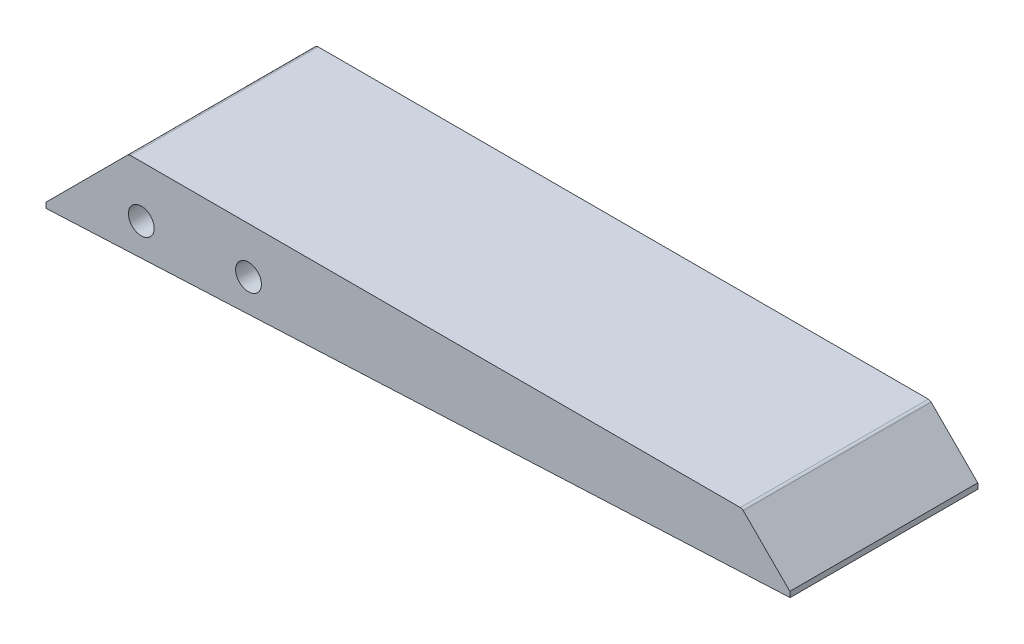
SolidWorks part; units mm, degrees
ref_plane "前视基准面" through (0, 0, 0) normal (0, 0, 1) x (1, 0, 0)
ref_plane "上视基准面" through (0, 0, 0) normal (0, 1, 0) x (1, 0, 0)
ref_plane "右视基准面" through (0, 0, 0) normal (1, 0, 0) x (0, 0, -1)
other "Configuration Table"
sketch "草图1" plane through (0, 0, 0) normal (0, 0, 1) x (1, 0, 0)
  line L0 (168.3324, 7.5944) -> (170.4537, 9.7157) construction
  line L1 (170.4537, 9.7157) -> (161.7639, 18.4056) construction
  line L2 (159.6425, 16.2843) -> (168.3324, 7.5944) construction
  line L3 (159.1217, 19.5) -> (45.4745, 19.5) construction
  line L4 (45.4745, 16.5) -> (159.1217, 16.5) construction
  line L5 (29.7639, 1.0944) -> (44.9537, 16.2843) construction
  line L6 (42.8324, 18.4056) -> (27.6425, 3.2157) construction
  line L7 (27.6425, 3.2157) -> (29.7639, 1.0944) construction
  line L8 (168.3324, 7.5944) -> (170.4537, 9.7157)
  line L9 (170.4537, 9.7157) -> (161.7639, 18.4056)
  line L10 (159.6425, 16.2843) -> (168.3324, 7.5944)
  line L11 (159.1217, 19.5) -> (45.4745, 19.5)
  line L12 (45.4745, 16.5) -> (159.1217, 16.5)
  line L13 (29.7639, 1.0944) -> (44.9537, 16.2843)
  line L14 (42.8324, 18.4056) -> (27.6425, 3.2157)
  line L15 (27.6425, 3.2157) -> (29.7639, 1.0944)
  line L16 (29.7639, 1.0944) -> (168.3324, 7.5944)
  arc A0 (159.6425, 16.2843) -> (159.1217, 16.5) centre (159.1217, 15.7634) ccw construction
  arc A1 (161.7639, 18.4056) -> (159.1217, 19.5) centre (159.1217, 15.7634) ccw construction
  arc A2 (45.4745, 16.5) -> (44.9537, 16.2843) centre (45.4745, 15.7634) ccw construction
  arc A3 (45.4745, 19.5) -> (42.8324, 18.4056) centre (45.4745, 15.7634) ccw construction
  arc A4 (159.6425, 16.2843) -> (159.1217, 16.5) centre (159.1217, 15.7634) ccw
  arc A5 (161.7639, 18.4056) -> (159.1217, 19.5) centre (159.1217, 15.7634) ccw
  arc A6 (45.4745, 16.5) -> (44.9537, 16.2843) centre (45.4745, 15.7634) ccw
  arc A7 (45.4745, 19.5) -> (42.8324, 18.4056) centre (45.4745, 15.7634) ccw
extrude "凸台-拉伸1" add sketch "草图1" against normal blind 35 contours L12 A6 L13 L16 L10 A4 region at (95.4976, 10.1082, 0)
sketch "草图2" plane through (0.0141, -0.3011, 0) normal (0.0469, -0.9989, 0) x (0.9989, 0.0469, 0)
  line L0 (167.0033, -1.5) -> (31.2825, -1.5)
  line L1 (31.2825, -1.5) -> (31.2825, -33.5)
  line L2 (31.2825, -33.5) -> (167.0033, -33.5)
  line L3 (167.0033, -33.5) -> (167.0033, -1.5)
  line L4 (168.5033, 0) -> (29.7825, 0)
  line L5 (29.7825, 0) -> (29.7825, -35)
  line L6 (29.7825, -35) -> (168.5033, -35)
  line L7 (168.5033, -35) -> (168.5033, 0)
  line L8 (168.5033, 0) -> (29.7825, 0)
  line L9 (29.7825, 0) -> (29.7825, -35)
  line L10 (29.7825, -35) -> (168.5033, -35)
  line L11 (168.5033, -35) -> (168.5033, 0)
  dimension "D1" = 0
  dimension "D2" = 1.5
extrude "凸台-拉伸2" add sketch "草图2" along normal blind 1
fillet "圆角1" radius 2 4 edges at (31.2856, 0.6653, -33.5) (166.8575, 7.0247, -33.5) (166.8575, 7.0247, -1.5) (31.2856, 0.6653, -1.5)
sketch "草图3" plane through (0, 0, 0) normal (0, 0, 1) x (1, 0, 0)
  line L0 (168.3792, 6.5955) -> (29.8107, 0.0955) construction
  line L1 (29.8107, 0.0955) -> (29.7639, 1.0944) construction
  circle A0 centre (47.5098, 6.9324) radius 2.4
  circle A1 centre (67.4872, 7.8832) radius 2.4
  dimension "D1" = 4.8
  dimension "D3" = 20
  dimension "D4" = 6
  dimension "D5" = 18
  dimension "D2" = 2
extrude "切除-拉伸1" cut sketch "草图3" against normal blind 6.2
sketch "草图4" plane through (0, 0, -35) normal (0, 0, -1) x (-1, 0, 0)
  circle A0 centre (-47.5098, 6.9324) radius 2.4 construction
  circle A1 centre (-67.4872, 7.8832) radius 2.4 construction
  circle A2 centre (-47.5098, 6.9324) radius 2.4
  circle A3 centre (-67.4872, 7.8832) radius 2.4
extrude "切除-拉伸2" cut sketch "草图4" against normal blind 6.55
sketch "草图6" plane through (0.0141, -0.3011, 0) normal (0.0469, -0.9989, 0) x (0.9989, 0.0469, 0)
  line L1199 (144.5332, -18.3417) -> (144.2984, -18.2008)
  line L1200 (144.2984, -18.2008) -> (143.9227, -18.2947)
  line L1201 (143.9227, -18.2947) -> (142.7956, -19.4688)
  line L1202 (142.7956, -19.4688) -> (142.279, -19.8915)
  line L1203 (142.279, -19.8915) -> (142.1381, -19.8915)
  line L1204 (142.1381, -19.8915) -> (142.0911, -19.7506)
  line L1205 (142.0911, -19.7506) -> (142.6547, -18.2478)
  line L1206 (142.6547, -18.2478) -> (142.7016, -17.8251)
  line L1207 (142.7016, -17.8251) -> (142.4668, -17.4963)
  line L1208 (142.4668, -17.4963) -> (141.9972, -17.4494)
  line L1209 (141.9972, -17.4494) -> (141.6684, -17.7312)
  line L1210 (141.6684, -17.7312) -> (141.2457, -18.3887)
  line L1211 (141.2457, -18.3887) -> (140.2595, -19.3749)
  line L1212 (140.2595, -19.3749) -> (139.2263, -20.1263)
  line L1213 (139.2263, -20.1263) -> (138.8036, -20.3142)
  line L1214 (138.8036, -20.3142) -> (138.6157, -20.3142)
  line L1215 (138.6157, -20.3142) -> (138.5218, -20.2203)
  line L1216 (138.5218, -20.2203) -> (138.5218, -19.9854)
  line L1217 (138.5218, -19.9854) -> (138.6627, -19.6097)
  line L1218 (138.6627, -19.6097) -> (139.4611, -18.4356)
  line L1219 (139.4611, -18.4356) -> (139.4611, -18.1069)
  line L1220 (139.4611, -18.1069) -> (139.2732, -17.872)
  line L1221 (139.2732, -17.872) -> (139.0384, -17.7781)
  line L1222 (139.0384, -17.7781) -> (138.6627, -17.872)
  line L1223 (138.6627, -17.872) -> (138.0052, -18.6235)
  line L1224 (138.0052, -18.6235) -> (137.5825, -19.3279)
  line L1225 (137.5825, -19.3279) -> (137.3477, -20.1263)
  line L1226 (137.3477, -20.1263) -> (137.3477, -20.4081)
  line L1227 (137.3477, -20.4081) -> (137.4886, -20.7838)
  line L1228 (137.4886, -20.7838) -> (137.9113, -21.1595)
  line L1229 (137.9113, -21.1595) -> (138.1931, -21.2535)
  line L1230 (138.1931, -21.2535) -> (138.7566, -21.2535)
  line L1231 (138.7566, -21.2535) -> (139.6959, -20.8778)
  line L1232 (139.6959, -20.8778) -> (140.6352, -20.1733)
  line L1233 (140.6352, -20.1733) -> (140.7761, -20.2203)
  line L1234 (140.7761, -20.2203) -> (140.6352, -20.8308)
  line L1235 (140.6352, -20.8308) -> (140.5413, -20.9247)
  line L1236 (140.5413, -20.9247) -> (138.5218, -21.817)
  line L1237 (138.5218, -21.817) -> (137.9582, -22.1928)
  line L1238 (137.9582, -22.1928) -> (137.6295, -22.5215)
  line L1239 (137.6295, -22.5215) -> (137.4416, -22.8503)
  line L1240 (137.4416, -22.8503) -> (137.4416, -23.2729)
  line L1241 (137.4416, -23.2729) -> (137.6765, -23.6487)
  line L1242 (137.6765, -23.6487) -> (138.0052, -23.8835)
  line L1243 (138.0052, -23.8835) -> (138.3809, -24.0244)
  line L1244 (138.3809, -24.0244) -> (139.1793, -24.0713)
  line L1245 (139.1793, -24.0713) -> (139.8368, -23.8835)
  line L1246 (139.8368, -23.8835) -> (140.4473, -23.5078)
  line L1247 (140.4473, -23.5078) -> (141.0109, -22.8503)
  line L1248 (141.0109, -22.8503) -> (141.4806, -21.817)
  line L1249 (141.4806, -21.817) -> (141.6215, -21.3004)
  line L1250 (141.6215, -21.3004) -> (142.8425, -20.596)
  line L1251 (142.8425, -20.596) -> (143.7348, -19.8445)
  line L1252 (143.7348, -19.8445) -> (144.4863, -18.9522)
  line L1253 (144.4863, -18.9522) -> (144.5802, -18.7644)
  line L1254 (144.5802, -18.7644) -> (144.5332, -18.3417)
  line L1255 (140.2125, -21.9579) -> (140.2125, -22.0988)
  line L1256 (140.2125, -22.0988) -> (140.0247, -22.4745)
  line L1257 (140.0247, -22.4745) -> (139.555, -22.9912)
  line L1258 (139.555, -22.9912) -> (139.0854, -23.226)
  line L1259 (139.0854, -23.226) -> (138.6627, -23.226)
  line L1260 (138.6627, -23.226) -> (138.5218, -23.0851)
  line L1261 (138.5218, -23.0851) -> (138.5688, -22.8503)
  line L1262 (138.5688, -22.8503) -> (138.8036, -22.5685)
  line L1263 (138.8036, -22.5685) -> (140.0716, -21.911)
  line L1264 (140.0716, -21.911) -> (140.2125, -21.9579)
  line L1265 (156.9788, -14.8663) -> (156.744, -14.7254)
  line L1266 (156.744, -14.7254) -> (156.4152, -14.7254)
  line L1267 (156.4152, -14.7254) -> (156.1334, -14.9133)
  line L1268 (156.1334, -14.9133) -> (156.0395, -15.1481)
  line L1269 (156.0395, -15.1481) -> (155.9925, -16.0874)
  line L1270 (155.9925, -16.0874) -> (155.5698, -17.1676)
  line L1271 (155.5698, -17.1676) -> (154.7715, -18.3417)
  line L1272 (154.7715, -18.3417) -> (153.9731, -19.0462)
  line L1273 (153.9731, -19.0462) -> (153.6913, -18.9992)
  line L1274 (153.6913, -18.9992) -> (153.6913, -18.3417)
  line L1275 (153.6913, -18.3417) -> (153.8791, -17.7312)
  line L1276 (153.8791, -17.7312) -> (153.8791, -17.3085)
  line L1277 (153.8791, -17.3085) -> (153.6913, -17.0736)
  line L1278 (153.6913, -17.0736) -> (153.5034, -16.9797)
  line L1279 (153.5034, -16.9797) -> (153.2686, -16.9797)
  line L1280 (153.2686, -16.9797) -> (153.0338, -17.0736)
  line L1281 (153.0338, -17.0736) -> (152.8459, -17.2615)
  line L1282 (152.8459, -17.2615) -> (152.3763, -18.1069)
  line L1283 (152.3763, -18.1069) -> (151.39, -19.1401)
  line L1284 (151.39, -19.1401) -> (151.1082, -19.3279)
  line L1285 (151.1082, -19.3279) -> (150.9204, -19.281)
  line L1286 (150.9204, -19.281) -> (150.9673, -18.9053)
  line L1287 (150.9673, -18.9053) -> (151.2022, -18.2478)
  line L1288 (151.2022, -18.2478) -> (152.0006, -16.7919)
  line L1289 (152.0006, -16.7919) -> (151.9536, -16.3692)
  line L1290 (151.9536, -16.3692) -> (151.5779, -16.1344)
  line L1291 (151.5779, -16.1344) -> (151.2022, -16.2283)
  line L1292 (151.2022, -16.2283) -> (150.9204, -16.5101)
  line L1293 (150.9204, -16.5101) -> (150.122, -17.872)
  line L1294 (150.122, -17.872) -> (149.8872, -18.6235)
  line L1295 (149.8872, -18.6235) -> (149.0418, -19.4219)
  line L1296 (149.0418, -19.4219) -> (148.4782, -19.8445)
  line L1297 (148.4782, -19.8445) -> (148.2434, -19.9385)
  line L1298 (148.2434, -19.9385) -> (147.9616, -19.9385)
  line L1299 (147.9616, -19.9385) -> (147.7268, -19.7976)
  line L1300 (147.7268, -19.7976) -> (147.3511, -19.4219)
  line L1301 (147.3511, -19.4219) -> (147.3511, -19.281)
  line L1302 (147.3511, -19.281) -> (149.1827, -17.5433)
  line L1303 (149.1827, -17.5433) -> (149.2766, -17.3554)
  line L1304 (149.2766, -17.3554) -> (149.2766, -17.1206)
  line L1305 (149.2766, -17.1206) -> (149.0418, -16.8388)
  line L1306 (149.0418, -16.8388) -> (148.6661, -16.7919)
  line L1307 (148.6661, -16.7919) -> (148.3373, -16.9328)
  line L1308 (148.3373, -16.9328) -> (146.6466, -18.4826)
  line L1309 (146.6466, -18.4826) -> (146.5057, -18.4826)
  line L1310 (146.5057, -18.4826) -> (145.6604, -17.5433)
  line L1311 (145.6604, -17.5433) -> (145.1907, -17.4963)
  line L1312 (145.1907, -17.4963) -> (145.0029, -17.5903)
  line L1313 (145.0029, -17.5903) -> (144.815, -17.8251)
  line L1314 (144.815, -17.8251) -> (144.815, -18.1069)
  line L1315 (144.815, -18.1069) -> (145.7543, -19.281)
  line L1316 (145.7543, -19.281) -> (145.7543, -19.3749)
  line L1317 (145.7543, -19.3749) -> (144.1106, -21.2065)
  line L1318 (144.1106, -21.2065) -> (143.9227, -21.5822)
  line L1319 (143.9227, -21.5822) -> (143.9697, -21.864)
  line L1320 (143.9697, -21.864) -> (144.2515, -22.0988)
  line L1321 (144.2515, -22.0988) -> (144.5802, -22.0988)
  line L1322 (144.5802, -22.0988) -> (144.815, -22.0049)
  line L1323 (144.815, -22.0049) -> (146.4588, -20.2203)
  line L1324 (146.4588, -20.2203) -> (146.5997, -20.2203)
  line L1325 (146.5997, -20.2203) -> (147.0693, -20.6429)
  line L1326 (147.0693, -20.6429) -> (147.492, -20.8778)
  line L1327 (147.492, -20.8778) -> (148.2904, -20.9247)
  line L1328 (148.2904, -20.9247) -> (149.0888, -20.549)
  line L1329 (149.0888, -20.549) -> (149.7463, -19.9385)
  line L1330 (149.7463, -19.9385) -> (149.8872, -19.9385)
  line L1331 (149.8872, -19.9385) -> (150.169, -20.2672)
  line L1332 (150.169, -20.2672) -> (150.4038, -20.4081)
  line L1333 (150.4038, -20.4081) -> (150.9204, -20.4551)
  line L1334 (150.9204, -20.4551) -> (151.2491, -20.3611)
  line L1335 (151.2491, -20.3611) -> (151.8127, -20.0324)
  line L1336 (151.8127, -20.0324) -> (152.5172, -19.3749)
  line L1337 (152.5172, -19.3749) -> (152.6581, -19.4219)
  line L1338 (152.6581, -19.4219) -> (152.752, -19.6567)
  line L1339 (152.752, -19.6567) -> (153.0338, -19.9385)
  line L1340 (153.0338, -19.9385) -> (153.4565, -20.1263)
  line L1341 (153.4565, -20.1263) -> (154.067, -20.0794)
  line L1342 (154.067, -20.0794) -> (154.5366, -19.8915)
  line L1343 (154.5366, -19.8915) -> (155.2881, -19.3279)
  line L1344 (155.2881, -19.3279) -> (155.7577, -18.8583)
  line L1345 (155.7577, -18.8583) -> (156.2743, -18.1538)
  line L1346 (156.2743, -18.1538) -> (156.744, -17.3085)
  line L1347 (156.744, -17.3085) -> (157.1197, -16.0404)
  line L1348 (157.1197, -16.0404) -> (157.1197, -15.1951)
  line L1349 (157.1197, -15.1951) -> (156.9788, -14.8663)
  line L1599 (103.178, -10.8157) -> (102.5205, -10.4869)
  line L1600 (102.5205, -10.4869) -> (101.7221, -10.2521)
  line L1601 (101.7221, -10.2521) -> (100.2192, -10.2521)
  line L1602 (100.2192, -10.2521) -> (99.5148, -10.5339)
  line L1603 (99.5148, -10.5339) -> (99.0921, -10.8626)
  line L1604 (99.0921, -10.8626) -> (97.4014, -11.6141)
  line L1605 (97.4014, -11.6141) -> (95.8985, -12.1307)
  line L1606 (95.8985, -12.1307) -> (94.8653, -12.2716)
  line L1607 (94.8653, -12.2716) -> (94.6305, -12.4594)
  line L1608 (94.6305, -12.4594) -> (94.5365, -12.6473)
  line L1609 (94.5365, -12.6473) -> (94.5835, -12.9291)
  line L1610 (94.5835, -12.9291) -> (95.0531, -13.3987)
  line L1611 (95.0531, -13.3987) -> (95.4289, -13.5866)
  line L1612 (95.4289, -13.5866) -> (96.0864, -13.7744)
  line L1613 (96.0864, -13.7744) -> (97.6362, -13.7744)
  line L1614 (97.6362, -13.7744) -> (97.824, -14.1032)
  line L1615 (97.824, -14.1032) -> (97.871, -14.9955)
  line L1616 (97.871, -14.9955) -> (97.7771, -15.3242)
  line L1617 (97.7771, -15.3242) -> (96.556, -15.7939)
  line L1618 (96.556, -15.7939) -> (95.8046, -16.2635)
  line L1619 (95.8046, -16.2635) -> (94.9592, -15.9817)
  line L1620 (94.9592, -15.9817) -> (94.4896, -15.9817)
  line L1621 (94.4896, -15.9817) -> (94.1608, -16.1226)
  line L1622 (94.1608, -16.1226) -> (94.0199, -16.2635)
  line L1623 (94.0199, -16.2635) -> (93.926, -16.5453)
  line L1624 (93.926, -16.5453) -> (94.2078, -17.4846)
  line L1625 (94.2078, -17.4846) -> (94.2548, -18.8935)
  line L1626 (94.2548, -18.8935) -> (94.3956, -19.7389)
  line L1627 (94.3956, -19.7389) -> (94.6305, -20.3964)
  line L1628 (94.6305, -20.3964) -> (94.9123, -20.866)
  line L1629 (94.9123, -20.866) -> (95.4758, -21.4296)
  line L1630 (95.4758, -21.4296) -> (95.9924, -21.6644)
  line L1631 (95.9924, -21.6644) -> (96.603, -21.7114)
  line L1632 (96.603, -21.7114) -> (97.3544, -21.4766)
  line L1633 (97.3544, -21.4766) -> (97.5423, -21.4766)
  line L1634 (97.5423, -21.4766) -> (97.5892, -21.6644)
  line L1635 (97.5892, -21.6644) -> (97.4483, -22.3219)
  line L1636 (97.4483, -22.3219) -> (97.2605, -22.7916)
  line L1637 (97.2605, -22.7916) -> (96.7908, -23.3551)
  line L1638 (96.7908, -23.3551) -> (95.1471, -23.8248)
  line L1639 (95.1471, -23.8248) -> (93.6442, -24.1066)
  line L1640 (93.6442, -24.1066) -> (92.7519, -24.1535)
  line L1641 (92.7519, -24.1535) -> (92.4701, -24.2944)
  line L1642 (92.4701, -24.2944) -> (92.1883, -24.6232)
  line L1643 (92.1883, -24.6232) -> (92.0944, -25.0928)
  line L1644 (92.0944, -25.0928) -> (92.3292, -25.6564)
  line L1645 (92.3292, -25.6564) -> (92.7519, -26.0791)
  line L1646 (92.7519, -26.0791) -> (93.4094, -26.4548)
  line L1647 (93.4094, -26.4548) -> (93.973, -26.6426)
  line L1648 (93.973, -26.6426) -> (95.5228, -26.6426)
  line L1649 (95.5228, -26.6426) -> (96.4621, -26.4078)
  line L1650 (96.4621, -26.4078) -> (100.5949, -24.905)
  line L1651 (100.5949, -24.905) -> (102.9431, -24.2005)
  line L1652 (102.9431, -24.2005) -> (103.3658, -24.2475)
  line L1653 (103.3658, -24.2475) -> (103.9764, -25.2807)
  line L1654 (103.9764, -25.2807) -> (104.446, -25.7034)
  line L1655 (104.446, -25.7034) -> (104.9156, -25.9382)
  line L1656 (104.9156, -25.9382) -> (105.3853, -26.0321)
  line L1657 (105.3853, -26.0321) -> (105.9019, -25.9851)
  line L1658 (105.9019, -25.9851) -> (106.4185, -25.7503)
  line L1659 (106.4185, -25.7503) -> (106.7942, -25.3746)
  line L1660 (106.7942, -25.3746) -> (107.029, -24.7641)
  line L1661 (107.029, -24.7641) -> (107.029, -24.2005)
  line L1662 (107.029, -24.2005) -> (106.8881, -23.6839)
  line L1663 (106.8881, -23.6839) -> (106.5594, -23.1203)
  line L1664 (106.5594, -23.1203) -> (105.8549, -22.3689)
  line L1665 (105.8549, -22.3689) -> (104.9156, -21.7114)
  line L1666 (104.9156, -21.7114) -> (103.8824, -21.2417)
  line L1667 (103.8824, -21.2417) -> (103.178, -21.0539)
  line L1668 (103.178, -21.0539) -> (102.6144, -21.1009)
  line L1669 (102.6144, -21.1009) -> (102.4265, -21.1948)
  line L1670 (102.4265, -21.1948) -> (102.2387, -21.4766)
  line L1671 (102.2387, -21.4766) -> (102.3326, -21.8523)
  line L1672 (102.3326, -21.8523) -> (102.6144, -22.181)
  line L1673 (102.6144, -22.181) -> (102.5205, -22.3689)
  line L1674 (102.5205, -22.3689) -> (101.2524, -22.5567)
  line L1675 (101.2524, -22.5567) -> (100.2662, -22.7916)
  line L1676 (100.2662, -22.7916) -> (99.9374, -22.7446)
  line L1677 (99.9374, -22.7446) -> (99.9374, -22.6037)
  line L1678 (99.9374, -22.6037) -> (100.2662, -21.9462)
  line L1679 (100.2662, -21.9462) -> (100.5949, -20.7721)
  line L1680 (100.5949, -20.7721) -> (100.7358, -20.6782)
  line L1681 (100.7358, -20.6782) -> (101.5342, -20.4903)
  line L1682 (101.5342, -20.4903) -> (102.8492, -20.3494)
  line L1683 (102.8492, -20.3494) -> (103.5067, -20.1146)
  line L1684 (103.5067, -20.1146) -> (103.8355, -19.7859)
  line L1685 (103.8355, -19.7859) -> (103.9764, -19.4571)
  line L1686 (103.9764, -19.4571) -> (104.5399, -18.6587)
  line L1687 (104.5399, -18.6587) -> (105.3383, -17.015)
  line L1688 (105.3383, -17.015) -> (105.3383, -16.3575)
  line L1689 (105.3383, -16.3575) -> (105.2444, -16.0757)
  line L1690 (105.2444, -16.0757) -> (105.0096, -15.7)
  line L1691 (105.0096, -15.7) -> (104.1642, -14.9955)
  line L1692 (104.1642, -14.9955) -> (103.6006, -14.7137)
  line L1693 (103.6006, -14.7137) -> (102.5674, -14.4319)
  line L1694 (102.5674, -14.4319) -> (101.5812, -14.4319)
  line L1695 (101.5812, -14.4319) -> (101.2524, -14.5259)
  line L1696 (101.2524, -14.5259) -> (100.8298, -14.4789)
  line L1697 (100.8298, -14.4789) -> (100.7828, -13.9623)
  line L1698 (100.7828, -13.9623) -> (100.6889, -13.7744)
  line L1699 (100.6889, -13.7744) -> (100.6889, -13.6335)
  line L1700 (100.6889, -13.6335) -> (100.7828, -13.5396)
  line L1701 (100.7828, -13.5396) -> (103.2249, -12.9291)
  line L1702 (103.2249, -12.9291) -> (103.7885, -12.4594)
  line L1703 (103.7885, -12.4594) -> (103.9294, -12.1307)
  line L1704 (103.9294, -12.1307) -> (103.8824, -11.6141)
  line L1705 (103.8824, -11.6141) -> (103.7415, -11.3323)
  line L1706 (103.7415, -11.3323) -> (103.178, -10.8157)
  line L1707 (97.7301, -17.2967) -> (97.7301, -19.3162)
  line L1708 (97.7301, -19.3162) -> (97.4014, -19.551)
  line L1709 (97.4014, -19.551) -> (96.8848, -19.598)
  line L1710 (96.8848, -19.598) -> (96.6969, -19.4571)
  line L1711 (96.6969, -19.4571) -> (96.556, -19.0344)
  line L1712 (96.556, -19.0344) -> (96.509, -17.9073)
  line L1713 (96.509, -17.9073) -> (96.6499, -17.7664)
  line L1714 (96.6499, -17.7664) -> (97.5892, -17.2967)
  line L1715 (97.5892, -17.2967) -> (97.7301, -17.2967)
  line L1716 (101.816, -16.3575) -> (102.0508, -16.5453)
  line L1717 (102.0508, -16.5453) -> (102.0978, -16.6862)
  line L1718 (102.0978, -16.6862) -> (102.0508, -17.0619)
  line L1719 (102.0508, -17.0619) -> (101.863, -17.5785)
  line L1720 (101.863, -17.5785) -> (101.3933, -18.3769)
  line L1721 (101.3933, -18.3769) -> (101.0646, -18.6118)
  line L1722 (101.0646, -18.6118) -> (100.7828, -18.6587)
  line L1723 (100.7828, -18.6587) -> (100.7358, -18.1891)
  line L1724 (100.7358, -18.1891) -> (100.8298, -16.5923)
  line L1725 (100.8298, -16.5923) -> (100.9237, -16.4984)
  line L1726 (100.9237, -16.4984) -> (101.2524, -16.4044)
  line L1727 (101.2524, -16.4044) -> (101.816, -16.3575)
  line L1728 (128.0221, -9.9703) -> (127.5524, -9.9234)
  line L1729 (127.5524, -9.9234) -> (126.9419, -10.2991)
  line L1730 (126.9419, -10.2991) -> (124.7815, -12.4594)
  line L1731 (124.7815, -12.4594) -> (124.6406, -12.4594)
  line L1732 (124.6406, -12.4594) -> (123.2787, -10.8626)
  line L1733 (123.2787, -10.8626) -> (122.9969, -10.7218)
  line L1734 (122.9969, -10.7218) -> (122.7151, -10.7218)
  line L1735 (122.7151, -10.7218) -> (122.3394, -10.9566)
  line L1736 (122.3394, -10.9566) -> (122.2455, -11.3323)
  line L1737 (122.2455, -11.3323) -> (122.3864, -11.661)
  line L1738 (122.3864, -11.661) -> (123.7483, -13.3987)
  line L1739 (123.7483, -13.3987) -> (123.7483, -13.5396)
  line L1740 (123.7483, -13.5396) -> (122.1515, -15.4182)
  line L1741 (122.1515, -15.4182) -> (121.541, -16.3105)
  line L1742 (121.541, -16.3105) -> (121.3062, -16.7801)
  line L1743 (121.3062, -16.7801) -> (121.3062, -17.1559)
  line L1744 (121.3062, -17.1559) -> (121.4471, -17.3907)
  line L1745 (121.4471, -17.3907) -> (121.7289, -17.5316)
  line L1746 (121.7289, -17.5316) -> (122.0106, -17.5316)
  line L1747 (122.0106, -17.5316) -> (122.2455, -17.4376)
  line L1748 (122.2455, -17.4376) -> (122.4803, -17.2028)
  line L1749 (122.4803, -17.2028) -> (123.1378, -16.2166)
  line L1750 (123.1378, -16.2166) -> (124.5937, -14.4789)
  line L1751 (124.5937, -14.4789) -> (124.7346, -14.4789)
  line L1752 (124.7346, -14.4789) -> (125.439, -15.0894)
  line L1753 (125.439, -15.0894) -> (125.9556, -15.4182)
  line L1754 (125.9556, -15.4182) -> (126.4253, -15.4651)
  line L1755 (126.4253, -15.4651) -> (126.754, -15.2773)
  line L1756 (126.754, -15.2773) -> (126.848, -15.0894)
  line L1757 (126.848, -15.0894) -> (126.801, -14.7137)
  line L1758 (126.801, -14.7137) -> (125.5799, -13.5396)
  line L1759 (125.5799, -13.5396) -> (125.5799, -13.4457)
  line L1760 (125.5799, -13.4457) -> (128.069, -10.8626)
  line L1761 (128.069, -10.8626) -> (128.2569, -10.5339)
  line L1762 (128.2569, -10.5339) -> (128.2569, -10.2991)
  line L1763 (128.2569, -10.2991) -> (128.0221, -9.9703)
  line L1764 (132.2489, -9.5476) -> (131.8262, -9.4067)
  line L1765 (131.8262, -9.4067) -> (131.4505, -9.4067)
  line L1766 (131.4505, -9.4067) -> (130.9339, -9.5476)
  line L1767 (130.9339, -9.5476) -> (130.4642, -9.8294)
  line L1768 (130.4642, -9.8294) -> (130.3233, -9.8294)
  line L1769 (130.3233, -9.8294) -> (130.2764, -9.4067)
  line L1770 (130.2764, -9.4067) -> (129.9476, -9.078)
  line L1771 (129.9476, -9.078) -> (129.5719, -9.078)
  line L1772 (129.5719, -9.078) -> (129.384, -9.1719)
  line L1773 (129.384, -9.1719) -> (129.1962, -9.4067)
  line L1774 (129.1962, -9.4067) -> (128.2099, -12.1776)
  line L1775 (128.2099, -12.1776) -> (127.3646, -15.2773)
  line L1776 (127.3646, -15.2773) -> (126.848, -18.0012)
  line L1777 (126.848, -18.0012) -> (126.848, -18.6118)
  line L1778 (126.848, -18.6118) -> (127.0828, -18.9405)
  line L1779 (127.0828, -18.9405) -> (127.5055, -19.0344)
  line L1780 (127.5055, -19.0344) -> (127.7403, -18.9405)
  line L1781 (127.7403, -18.9405) -> (127.9751, -18.6587)
  line L1782 (127.9751, -18.6587) -> (128.2099, -17.1089)
  line L1783 (128.2099, -17.1089) -> (128.7735, -14.7607)
  line L1784 (128.7735, -14.7607) -> (129.6189, -14.7137)
  line L1785 (129.6189, -14.7137) -> (130.5112, -14.2441)
  line L1786 (130.5112, -14.2441) -> (130.8869, -13.9623)
  line L1787 (130.8869, -13.9623) -> (131.6853, -13.1639)
  line L1788 (131.6853, -13.1639) -> (132.3898, -12.1307)
  line L1789 (132.3898, -12.1307) -> (132.7185, -11.2853)
  line L1790 (132.7185, -11.2853) -> (132.8124, -10.5339)
  line L1791 (132.8124, -10.5339) -> (132.6246, -9.9234)
  line L1792 (132.6246, -9.9234) -> (132.2489, -9.5476)
  line L1793 (131.5444, -10.44) -> (131.6383, -10.6748)
  line L1794 (131.6383, -10.6748) -> (131.5914, -11.0035)
  line L1795 (131.5914, -11.0035) -> (131.4505, -11.4262)
  line L1796 (131.4505, -11.4262) -> (130.9808, -12.2246)
  line L1797 (130.9808, -12.2246) -> (130.0885, -13.2109)
  line L1798 (130.0885, -13.2109) -> (129.6658, -13.5396)
  line L1799 (129.6658, -13.5396) -> (129.1962, -13.7275)
  line L1800 (129.1962, -13.7275) -> (129.1492, -13.4926)
  line L1801 (129.1492, -13.4926) -> (129.431, -12.7412)
  line L1802 (129.431, -12.7412) -> (130.0415, -11.661)
  line L1803 (130.0415, -11.661) -> (130.8399, -10.7687)
  line L1804 (130.8399, -10.7687) -> (131.3565, -10.44)
  line L1805 (131.3565, -10.44) -> (131.5444, -10.44)
  line L1806 (46.3512, -7.6691) -> (46.2103, -8.0448)
  line L1807 (46.2103, -8.0448) -> (46.2103, -8.3266)
  line L1808 (46.2103, -8.3266) -> (46.4921, -8.8901)
  line L1809 (46.4921, -8.8901) -> (47.0556, -9.4537)
  line L1810 (47.0556, -9.4537) -> (48.6524, -10.6748)
  line L1811 (48.6524, -10.6748) -> (48.5115, -11.2384)
  line L1812 (48.5115, -11.2384) -> (47.8071, -12.7412)
  line L1813 (47.8071, -12.7412) -> (47.8071, -13.023)
  line L1814 (47.8071, -13.023) -> (47.9949, -13.2109)
  line L1815 (47.9949, -13.2109) -> (48.4176, -13.2109)
  line L1816 (48.4176, -13.2109) -> (49.3569, -12.5534)
  line L1817 (49.3569, -12.5534) -> (50.3431, -12.0368)
  line L1818 (50.3431, -12.0368) -> (50.8128, -11.8959)
  line L1819 (50.8128, -11.8959) -> (51.3764, -11.8959)
  line L1820 (51.3764, -11.8959) -> (51.9399, -11.755)
  line L1821 (51.9399, -11.755) -> (52.5974, -11.3792)
  line L1822 (52.5974, -11.3792) -> (52.9262, -11.0505)
  line L1823 (52.9262, -11.0505) -> (53.161, -10.6748)
  line L1824 (53.161, -10.6748) -> (53.3019, -10.0173)
  line L1825 (53.3019, -10.0173) -> (53.161, -9.4537)
  line L1826 (53.161, -9.4537) -> (52.9731, -9.125)
  line L1827 (52.9731, -9.125) -> (52.4565, -8.5614)
  line L1828 (52.4565, -8.5614) -> (52.0808, -8.2796)
  line L1829 (52.0808, -8.2796) -> (50.9537, -7.6691)
  line L1830 (50.9537, -7.6691) -> (49.8735, -7.2934)
  line L1831 (49.8735, -7.2934) -> (48.6524, -7.0585)
  line L1832 (48.6524, -7.0585) -> (47.1965, -7.1055)
  line L1833 (47.1965, -7.1055) -> (46.7269, -7.2934)
  line L1834 (46.7269, -7.2934) -> (46.3512, -7.6691)
  line L1835 (154.2281, -7.4342) -> (154.0403, -7.1994)
  line L1836 (154.0403, -7.1994) -> (153.6646, -7.1994)
  line L1837 (153.6646, -7.1994) -> (152.0678, -8.2796)
  line L1838 (152.0678, -8.2796) -> (151.5042, -8.5144)
  line L1839 (151.5042, -8.5144) -> (151.1755, -8.5614)
  line L1840 (151.1755, -8.5614) -> (151.0815, -8.4675)
  line L1841 (151.0815, -8.4675) -> (151.0815, -8.3266)
  line L1842 (151.0815, -8.3266) -> (151.5042, -7.0116)
  line L1843 (151.5042, -7.0116) -> (151.4573, -6.495)
  line L1844 (151.4573, -6.495) -> (151.2224, -6.2132)
  line L1845 (151.2224, -6.2132) -> (150.9876, -6.1193)
  line L1846 (150.9876, -6.1193) -> (150.518, -6.1662)
  line L1847 (150.518, -6.1662) -> (150.0014, -6.448)
  line L1848 (150.0014, -6.448) -> (149.2969, -7.0585)
  line L1849 (149.2969, -7.0585) -> (149.156, -7.0116)
  line L1850 (149.156, -7.0116) -> (149.109, -6.6359)
  line L1851 (149.109, -6.6359) -> (148.9212, -6.448)
  line L1852 (148.9212, -6.448) -> (148.4515, -6.401)
  line L1853 (148.4515, -6.401) -> (148.2167, -6.5419)
  line L1854 (148.2167, -6.5419) -> (148.0289, -6.8237)
  line L1855 (148.0289, -6.8237) -> (147.5123, -8.0448)
  line L1856 (147.5123, -8.0448) -> (146.7139, -8.8901)
  line L1857 (146.7139, -8.8901) -> (145.9624, -9.5476)
  line L1858 (145.9624, -9.5476) -> (145.8685, -9.5476)
  line L1859 (145.8685, -9.5476) -> (145.8215, -9.3128)
  line L1860 (145.8215, -9.3128) -> (146.573, -7.3873)
  line L1861 (146.573, -7.3873) -> (146.573, -7.1525)
  line L1862 (146.573, -7.1525) -> (146.3851, -6.8707)
  line L1863 (146.3851, -6.8707) -> (146.1973, -6.7767)
  line L1864 (146.1973, -6.7767) -> (145.9155, -6.7767)
  line L1865 (145.9155, -6.7767) -> (145.7276, -6.8707)
  line L1866 (145.7276, -6.8707) -> (145.4928, -7.1525)
  line L1867 (145.4928, -7.1525) -> (144.7883, -8.7492)
  line L1868 (144.7883, -8.7492) -> (144.6005, -9.5007)
  line L1869 (144.6005, -9.5007) -> (144.6005, -10.2051)
  line L1870 (144.6005, -10.2051) -> (144.9292, -10.6748)
  line L1871 (144.9292, -10.6748) -> (145.258, -10.8157)
  line L1872 (145.258, -10.8157) -> (145.5398, -10.8157)
  line L1873 (145.5398, -10.8157) -> (146.0564, -10.6278)
  line L1874 (146.0564, -10.6278) -> (147.0896, -9.7825)
  line L1875 (147.0896, -9.7825) -> (147.2305, -9.7825)
  line L1876 (147.2305, -9.7825) -> (147.3244, -9.9703)
  line L1877 (147.3244, -9.9703) -> (147.5123, -10.1112)
  line L1878 (147.5123, -10.1112) -> (147.9819, -10.1112)
  line L1879 (147.9819, -10.1112) -> (148.3576, -9.7825)
  line L1880 (148.3576, -9.7825) -> (148.7333, -9.2189)
  line L1881 (148.7333, -9.2189) -> (149.8135, -7.9509)
  line L1882 (149.8135, -7.9509) -> (149.9544, -7.9978)
  line L1883 (149.9544, -7.9978) -> (149.9074, -8.7962)
  line L1884 (149.9074, -8.7962) -> (150.0014, -9.078)
  line L1885 (150.0014, -9.078) -> (150.2362, -9.3598)
  line L1886 (150.2362, -9.3598) -> (150.7998, -9.5946)
  line L1887 (150.7998, -9.5946) -> (151.6451, -9.5007)
  line L1888 (151.6451, -9.5007) -> (152.6314, -9.078)
  line L1889 (152.6314, -9.078) -> (153.5237, -8.5144)
  line L1890 (153.5237, -8.5144) -> (153.9464, -8.1387)
  line L1891 (153.9464, -8.1387) -> (154.2281, -7.763)
  line L1892 (154.2281, -7.763) -> (154.2281, -7.4342)
  line L1893 (132.8594, -12.8821) -> (133.0003, -13.2109)
  line L1894 (133.0003, -13.2109) -> (133.2351, -13.4457)
  line L1895 (133.2351, -13.4457) -> (133.5639, -13.5866)
  line L1896 (133.5639, -13.5866) -> (133.8926, -13.5866)
  line L1897 (133.8926, -13.5866) -> (134.644, -13.2109)
  line L1898 (134.644, -13.2109) -> (135.5364, -12.3185)
  line L1899 (135.5364, -12.3185) -> (135.6303, -12.3185)
  line L1900 (135.6303, -12.3185) -> (135.7712, -12.5064)
  line L1901 (135.7712, -12.5064) -> (136.006, -12.6473)
  line L1902 (136.006, -12.6473) -> (136.5226, -12.6473)
  line L1903 (136.5226, -12.6473) -> (136.7574, -12.5534)
  line L1904 (136.7574, -12.5534) -> (137.0862, -12.3185)
  line L1905 (137.0862, -12.3185) -> (137.9315, -11.4262)
  line L1906 (137.9315, -11.4262) -> (138.0255, -11.4262)
  line L1907 (138.0255, -11.4262) -> (138.1664, -11.708)
  line L1908 (138.1664, -11.708) -> (138.4012, -11.8959)
  line L1909 (138.4012, -11.8959) -> (139.0117, -11.9428)
  line L1910 (139.0117, -11.9428) -> (139.6223, -11.5671)
  line L1911 (139.6223, -11.5671) -> (140.0449, -11.1444)
  line L1912 (140.0449, -11.1444) -> (140.7964, -10.2051)
  line L1913 (140.7964, -10.2051) -> (141.3599, -9.3598)
  line L1914 (141.3599, -9.3598) -> (142.0174, -9.6885)
  line L1915 (142.0174, -9.6885) -> (143.0976, -9.8294)
  line L1916 (143.0976, -9.8294) -> (143.1915, -10.0173)
  line L1917 (143.1915, -10.0173) -> (142.7689, -10.393)
  line L1918 (142.7689, -10.393) -> (142.0174, -10.6748)
  line L1919 (142.0174, -10.6748) -> (141.7356, -10.6748)
  line L1920 (141.7356, -10.6748) -> (141.4069, -10.393)
  line L1921 (141.4069, -10.393) -> (141.1721, -10.393)
  line L1922 (141.1721, -10.393) -> (140.9842, -10.4869)
  line L1923 (140.9842, -10.4869) -> (140.7964, -10.6748)
  line L1924 (140.7964, -10.6748) -> (140.7024, -10.9096)
  line L1925 (140.7024, -10.9096) -> (140.7024, -11.1444)
  line L1926 (140.7024, -11.1444) -> (140.7964, -11.3323)
  line L1927 (140.7964, -11.3323) -> (140.9842, -11.5201)
  line L1928 (140.9842, -11.5201) -> (141.5478, -11.708)
  line L1929 (141.5478, -11.708) -> (142.2992, -11.661)
  line L1930 (142.2992, -11.661) -> (143.1915, -11.3323)
  line L1931 (143.1915, -11.3323) -> (143.7081, -11.0035)
  line L1932 (143.7081, -11.0035) -> (144.1778, -10.5339)
  line L1933 (144.1778, -10.5339) -> (144.4126, -10.0642)
  line L1934 (144.4126, -10.0642) -> (144.4126, -9.7355)
  line L1935 (144.4126, -9.7355) -> (144.2248, -9.3128)
  line L1936 (144.2248, -9.3128) -> (143.943, -9.078)
  line L1937 (143.943, -9.078) -> (143.2855, -8.8432)
  line L1938 (143.2855, -8.8432) -> (142.534, -8.7492)
  line L1939 (142.534, -8.7492) -> (142.4871, -8.4675)
  line L1940 (142.4871, -8.4675) -> (143.0506, -7.9509)
  line L1941 (143.0506, -7.9509) -> (143.1915, -7.9978)
  line L1942 (143.1915, -7.9978) -> (143.2385, -8.2326)
  line L1943 (143.2385, -8.2326) -> (143.4264, -8.3735)
  line L1944 (143.4264, -8.3735) -> (143.849, -8.3266)
  line L1945 (143.849, -8.3266) -> (144.1308, -8.0918)
  line L1946 (144.1308, -8.0918) -> (144.4126, -7.6691)
  line L1947 (144.4126, -7.6691) -> (144.4596, -7.2934)
  line L1948 (144.4596, -7.2934) -> (144.3656, -7.0585)
  line L1949 (144.3656, -7.0585) -> (144.2248, -6.9176)
  line L1950 (144.2248, -6.9176) -> (143.896, -6.7767)
  line L1951 (143.896, -6.7767) -> (143.4264, -6.7767)
  line L1952 (143.4264, -6.7767) -> (142.8158, -6.9646)
  line L1953 (142.8158, -6.9646) -> (142.1583, -7.3403)
  line L1954 (142.1583, -7.3403) -> (141.4069, -8.0918)
  line L1955 (141.4069, -8.0918) -> (140.8903, -8.4675)
  line L1956 (140.8903, -8.4675) -> (139.2465, -10.5339)
  line L1957 (139.2465, -10.5339) -> (139.1056, -10.4869)
  line L1958 (139.1056, -10.4869) -> (139.1056, -10.346)
  line L1959 (139.1056, -10.346) -> (139.4344, -9.2189)
  line L1960 (139.4344, -9.2189) -> (139.4344, -8.7023)
  line L1961 (139.4344, -8.7023) -> (139.1526, -8.4205)
  line L1962 (139.1526, -8.4205) -> (138.683, -8.4675)
  line L1963 (138.683, -8.4675) -> (138.4481, -8.7023)
  line L1964 (138.4481, -8.7023) -> (138.0724, -9.5946)
  line L1965 (138.0724, -9.5946) -> (137.7437, -10.1112)
  line L1966 (137.7437, -10.1112) -> (136.8044, -11.2384)
  line L1967 (136.8044, -11.2384) -> (136.6635, -11.1914)
  line L1968 (136.6635, -11.1914) -> (136.6635, -11.0505)
  line L1969 (136.6635, -11.0505) -> (137.0392, -10.0642)
  line L1970 (137.0392, -10.0642) -> (137.274, -9.6416)
  line L1971 (137.274, -9.6416) -> (137.321, -9.125)
  line L1972 (137.321, -9.125) -> (137.0862, -8.8432)
  line L1973 (137.0862, -8.8432) -> (136.9453, -8.7962)
  line L1974 (136.9453, -8.7962) -> (136.5226, -8.8901)
  line L1975 (136.5226, -8.8901) -> (136.1469, -9.4067)
  line L1976 (136.1469, -9.4067) -> (135.7712, -10.1582)
  line L1977 (135.7712, -10.1582) -> (135.5364, -10.8626)
  line L1978 (135.5364, -10.8626) -> (135.0198, -11.4732)
  line L1979 (135.0198, -11.4732) -> (134.1274, -12.3655)
  line L1980 (134.1274, -12.3655) -> (134.0335, -12.3655)
  line L1981 (134.0335, -12.3655) -> (133.9865, -12.0837)
  line L1982 (133.9865, -12.0837) -> (134.0805, -11.5201)
  line L1983 (134.0805, -11.5201) -> (134.4092, -10.2991)
  line L1984 (134.4092, -10.2991) -> (135.4424, -7.81)
  line L1985 (135.4424, -7.81) -> (136.006, -6.0253)
  line L1986 (136.006, -6.0253) -> (136.006, -5.6966)
  line L1987 (136.006, -5.6966) -> (135.7712, -5.3678)
  line L1988 (135.7712, -5.3678) -> (135.2076, -5.3678)
  line L1989 (135.2076, -5.3678) -> (134.9258, -5.6496)
  line L1990 (134.9258, -5.6496) -> (134.5031, -6.401)
  line L1991 (134.5031, -6.401) -> (134.1274, -7.2464)
  line L1992 (134.1274, -7.2464) -> (133.4699, -9.125)
  line L1993 (133.4699, -9.125) -> (133.0473, -10.7218)
  line L1994 (133.0473, -10.7218) -> (132.8594, -11.755)
  line L1995 (132.8594, -11.755) -> (132.8594, -12.8821)
  line L1996 (146.9956, -4.8982) -> (146.573, -4.8982)
  line L1997 (146.573, -4.8982) -> (146.1033, -5.3209)
  line L1998 (146.1033, -5.3209) -> (145.8215, -5.9314)
  line L1999 (145.8215, -5.9314) -> (145.8685, -6.2601)
  line L2000 (145.8685, -6.2601) -> (146.0564, -6.495)
  line L2001 (146.0564, -6.495) -> (146.4321, -6.5889)
  line L2002 (146.4321, -6.5889) -> (146.7608, -6.448)
  line L2003 (146.7608, -6.448) -> (147.1365, -5.9314)
  line L2004 (147.1365, -5.9314) -> (147.3244, -5.3678)
  line L2005 (147.3244, -5.3678) -> (147.2305, -5.086)
  line L2006 (147.2305, -5.086) -> (146.9956, -4.8982)
  line L2007 (83.1712, -24.2944) -> (82.9833, -24.0126)
  line L2008 (82.9833, -24.0126) -> (82.7955, -23.9187)
  line L2009 (82.7955, -23.9187) -> (82.4198, -23.9187)
  line L2010 (82.4198, -23.9187) -> (76.0796, -25.1868)
  line L2011 (76.0796, -25.1868) -> (73.6844, -25.5625)
  line L2012 (73.6844, -25.5625) -> (71.1483, -25.8442)
  line L2013 (71.1483, -25.8442) -> (69.6455, -25.9382)
  line L2014 (69.6455, -25.9382) -> (67.1094, -25.9382)
  line L2015 (67.1094, -25.9382) -> (65.1839, -25.7973)
  line L2016 (65.1839, -25.7973) -> (64.7142, -25.7034)
  line L2017 (64.7142, -25.7034) -> (64.7612, -25.5625)
  line L2018 (64.7612, -25.5625) -> (65.2778, -25.5625)
  line L2019 (65.2778, -25.5625) -> (66.264, -25.1868)
  line L2020 (66.264, -25.1868) -> (67.2033, -24.3414)
  line L2021 (67.2033, -24.3414) -> (67.579, -23.8248)
  line L2022 (67.579, -23.8248) -> (68.0956, -22.7916)
  line L2023 (68.0956, -22.7916) -> (68.3774, -22.0401)
  line L2024 (68.3774, -22.0401) -> (68.7062, -20.7721)
  line L2025 (68.7062, -20.7721) -> (68.941, -19.3162)
  line L2026 (68.941, -19.3162) -> (69.1758, -19.3162)
  line L2027 (69.1758, -19.3162) -> (70.209, -19.7389)
  line L2028 (70.209, -19.7389) -> (71.7119, -20.4903)
  line L2029 (71.7119, -20.4903) -> (74.5767, -22.1341)
  line L2030 (74.5767, -22.1341) -> (75.9856, -22.6037)
  line L2031 (75.9856, -22.6037) -> (76.9719, -22.6037)
  line L2032 (76.9719, -22.6037) -> (77.6764, -22.3219)
  line L2033 (77.6764, -22.3219) -> (78.099, -21.9462)
  line L2034 (78.099, -21.9462) -> (78.3808, -21.3826)
  line L2035 (78.3808, -21.3826) -> (78.3808, -20.7721)
  line L2036 (78.3808, -20.7721) -> (78.2869, -20.4434)
  line L2037 (78.2869, -20.4434) -> (77.8173, -19.7389)
  line L2038 (77.8173, -19.7389) -> (77.3476, -19.3162)
  line L2039 (77.3476, -19.3162) -> (75.9856, -18.5178)
  line L2040 (75.9856, -18.5178) -> (74.3419, -17.9073)
  line L2041 (74.3419, -17.9073) -> (72.6512, -17.4846)
  line L2042 (72.6512, -17.4846) -> (70.5848, -17.1559)
  line L2043 (70.5848, -17.1559) -> (69.1289, -17.0619)
  line L2044 (69.1289, -17.0619) -> (68.894, -16.968)
  line L2045 (68.894, -16.968) -> (68.941, -16.8271)
  line L2046 (68.941, -16.8271) -> (70.8196, -16.1226)
  line L2047 (70.8196, -16.1226) -> (72.1815, -15.4182)
  line L2048 (72.1815, -15.4182) -> (73.3556, -14.6198)
  line L2049 (73.3556, -14.6198) -> (74.201, -13.7744)
  line L2050 (74.201, -13.7744) -> (74.4828, -13.2578)
  line L2051 (74.4828, -13.2578) -> (74.5298, -12.5064)
  line L2052 (74.5298, -12.5064) -> (74.248, -11.8959)
  line L2053 (74.248, -11.8959) -> (73.6844, -11.3792)
  line L2054 (73.6844, -11.3792) -> (73.2148, -11.1444)
  line L2055 (73.2148, -11.1444) -> (72.5573, -10.9566)
  line L2056 (72.5573, -10.9566) -> (71.524, -10.9566)
  line L2057 (71.524, -10.9566) -> (70.6787, -11.2384)
  line L2058 (70.6787, -11.2384) -> (70.3969, -11.6141)
  line L2059 (70.3969, -11.6141) -> (70.4908, -11.9428)
  line L2060 (70.4908, -11.9428) -> (70.6787, -12.1307)
  line L2061 (70.6787, -12.1307) -> (70.6787, -12.3655)
  line L2062 (70.6787, -12.3655) -> (70.5378, -12.6473)
  line L2063 (70.5378, -12.6473) -> (69.5985, -13.8214)
  line L2064 (69.5985, -13.8214) -> (69.0349, -14.385)
  line L2065 (69.0349, -14.385) -> (68.0956, -15.1364)
  line L2066 (68.0956, -15.1364) -> (67.9078, -15.0425)
  line L2067 (67.9078, -15.0425) -> (67.579, -14.5259)
  line L2068 (67.579, -14.5259) -> (66.6398, -13.6335)
  line L2069 (66.6398, -13.6335) -> (66.0762, -13.2578)
  line L2070 (66.0762, -13.2578) -> (65.1369, -12.8351)
  line L2071 (65.1369, -12.8351) -> (65.1369, -12.7412)
  line L2072 (65.1369, -12.7412) -> (66.5928, -11.3792)
  line L2073 (66.5928, -11.3792) -> (67.2503, -10.5809)
  line L2074 (67.2503, -10.5809) -> (67.4381, -10.1582)
  line L2075 (67.4381, -10.1582) -> (67.4381, -9.6416)
  line L2076 (67.4381, -9.6416) -> (67.1564, -9.125)
  line L2077 (67.1564, -9.125) -> (67.2033, -8.9841)
  line L2078 (67.2033, -8.9841) -> (70.5848, -7.763)
  line L2079 (70.5848, -7.763) -> (71.1483, -7.4812)
  line L2080 (71.1483, -7.4812) -> (71.571, -7.0585)
  line L2081 (71.571, -7.0585) -> (71.7589, -6.7298)
  line L2082 (71.7589, -6.7298) -> (71.7589, -5.8375)
  line L2083 (71.7589, -5.8375) -> (71.524, -5.4148)
  line L2084 (71.524, -5.4148) -> (70.9135, -4.8982)
  line L2085 (70.9135, -4.8982) -> (70.256, -4.6164)
  line L2086 (70.256, -4.6164) -> (69.7864, -4.5225)
  line L2087 (69.7864, -4.5225) -> (68.894, -4.5225)
  line L2088 (68.894, -4.5225) -> (68.1896, -4.6634)
  line L2089 (68.1896, -4.6634) -> (67.3912, -4.9451)
  line L2090 (67.3912, -4.9451) -> (62.7417, -7.1525)
  line L2091 (62.7417, -7.1525) -> (60.2526, -8.1857)
  line L2092 (60.2526, -8.1857) -> (57.9983, -8.8901)
  line L2093 (57.9983, -8.8901) -> (56.8712, -9.078)
  line L2094 (56.8712, -9.078) -> (56.3076, -9.078)
  line L2095 (56.3076, -9.078) -> (56.0258, -9.2189)
  line L2096 (56.0258, -9.2189) -> (55.8849, -9.4537)
  line L2097 (55.8849, -9.4537) -> (55.9789, -9.8294)
  line L2098 (55.9789, -9.8294) -> (56.4485, -10.2051)
  line L2099 (56.4485, -10.2051) -> (56.9181, -10.44)
  line L2100 (56.9181, -10.44) -> (57.8105, -10.6748)
  line L2101 (57.8105, -10.6748) -> (58.7498, -10.7687)
  line L2102 (58.7498, -10.7687) -> (59.9239, -10.7218)
  line L2103 (59.9239, -10.7218) -> (61.1919, -10.5339)
  line L2104 (61.1919, -10.5339) -> (61.8494, -10.346)
  line L2105 (61.8494, -10.346) -> (62.0373, -10.346)
  line L2106 (62.0373, -10.346) -> (62.0842, -10.5339)
  line L2107 (62.0842, -10.5339) -> (61.2858, -11.5201)
  line L2108 (61.2858, -11.5201) -> (60.0648, -12.7412)
  line L2109 (60.0648, -12.7412) -> (59.1255, -13.5396)
  line L2110 (59.1255, -13.5396) -> (57.9983, -14.385)
  line L2111 (57.9983, -14.385) -> (56.8712, -15.0894)
  line L2112 (56.8712, -15.0894) -> (56.0258, -15.5121)
  line L2113 (56.0258, -15.5121) -> (55.5092, -15.653)
  line L2114 (55.5092, -15.653) -> (55.3214, -15.7939)
  line L2115 (55.3214, -15.7939) -> (55.2274, -16.0757)
  line L2116 (55.2274, -16.0757) -> (55.4153, -16.3105)
  line L2117 (55.4153, -16.3105) -> (55.744, -16.4514)
  line L2118 (55.744, -16.4514) -> (56.3546, -16.4984)
  line L2119 (56.3546, -16.4984) -> (57.9514, -16.2635)
  line L2120 (57.9514, -16.2635) -> (58.8437, -16.0287)
  line L2121 (58.8437, -16.0287) -> (59.8299, -15.653)
  line L2122 (59.8299, -15.653) -> (60.0648, -15.7)
  line L2123 (60.0648, -15.7) -> (59.9708, -15.9817)
  line L2124 (59.9708, -15.9817) -> (59.6421, -16.3575)
  line L2125 (59.6421, -16.3575) -> (58.1392, -17.6725)
  line L2126 (58.1392, -17.6725) -> (56.4485, -18.8466)
  line L2127 (56.4485, -18.8466) -> (55.838, -19.1753)
  line L2128 (55.838, -19.1753) -> (55.3214, -19.3162)
  line L2129 (55.3214, -19.3162) -> (55.0865, -19.645)
  line L2130 (55.0865, -19.645) -> (55.1805, -19.9268)
  line L2131 (55.1805, -19.9268) -> (55.6501, -20.2555)
  line L2132 (55.6501, -20.2555) -> (56.1667, -20.3964)
  line L2133 (56.1667, -20.3964) -> (57.106, -20.3964)
  line L2134 (57.106, -20.3964) -> (57.5756, -20.3025)
  line L2135 (57.5756, -20.3025) -> (58.5149, -19.9737)
  line L2136 (58.5149, -19.9737) -> (59.3603, -19.551)
  line L2137 (59.3603, -19.551) -> (60.5344, -18.7526)
  line L2138 (60.5344, -18.7526) -> (61.6146, -17.8134)
  line L2139 (61.6146, -17.8134) -> (61.7555, -17.8134)
  line L2140 (61.7555, -17.8134) -> (61.8494, -17.9073)
  line L2141 (61.8494, -17.9073) -> (61.8964, -18.1421)
  line L2142 (61.8964, -18.1421) -> (61.4267, -18.8466)
  line L2143 (61.4267, -18.8466) -> (60.6283, -19.6919)
  line L2144 (60.6283, -19.6919) -> (58.7967, -21.1948)
  line L2145 (58.7967, -21.1948) -> (57.7165, -21.8992)
  line L2146 (57.7165, -21.8992) -> (56.2606, -22.6507)
  line L2147 (56.2606, -22.6507) -> (55.3214, -23.0264)
  line L2148 (55.3214, -23.0264) -> (54.476, -23.2612)
  line L2149 (54.476, -23.2612) -> (54.2881, -23.496)
  line L2150 (54.2881, -23.496) -> (54.3351, -23.6839)
  line L2151 (54.3351, -23.6839) -> (54.6639, -23.9187)
  line L2152 (54.6639, -23.9187) -> (55.1805, -24.0126)
  line L2153 (55.1805, -24.0126) -> (56.4015, -23.9187)
  line L2154 (56.4015, -23.9187) -> (58.2331, -23.543)
  line L2155 (58.2331, -23.543) -> (60.7223, -22.6507)
  line L2156 (60.7223, -22.6507) -> (61.098, -23.4021)
  line L2157 (61.098, -23.4021) -> (62.0842, -24.4823)
  line L2158 (62.0842, -24.4823) -> (62.9765, -25.0928)
  line L2159 (62.9765, -25.0928) -> (63.5871, -25.3746)
  line L2160 (63.5871, -25.3746) -> (64.0098, -25.4685)
  line L2161 (64.0098, -25.4685) -> (64.0098, -25.6564)
  line L2162 (64.0098, -25.6564) -> (54.2881, -24.2944)
  line L2163 (54.2881, -24.2944) -> (51.4703, -24.0596)
  line L2164 (51.4703, -24.0596) -> (51.4233, -23.9187)
  line L2165 (51.4233, -23.9187) -> (51.893, -23.59)
  line L2166 (51.893, -23.59) -> (52.4565, -22.9325)
  line L2167 (52.4565, -22.9325) -> (52.6444, -22.5098)
  line L2168 (52.6444, -22.5098) -> (52.6914, -21.9932)
  line L2169 (52.6914, -21.9932) -> (52.4565, -21.3357)
  line L2170 (52.4565, -21.3357) -> (51.3294, -19.8798)
  line L2171 (51.3294, -19.8798) -> (51.2355, -19.551)
  line L2172 (51.2355, -19.551) -> (51.2355, -19.0814)
  line L2173 (51.2355, -19.0814) -> (51.3294, -18.7526)
  line L2174 (51.3294, -18.7526) -> (51.7051, -18.0951)
  line L2175 (51.7051, -18.0951) -> (53.208, -16.4514)
  line L2176 (53.208, -16.4514) -> (53.3958, -16.0287)
  line L2177 (53.3958, -16.0287) -> (53.3958, -15.7)
  line L2178 (53.3958, -15.7) -> (53.3019, -15.3712)
  line L2179 (53.3019, -15.3712) -> (53.114, -15.0894)
  line L2180 (53.114, -15.0894) -> (52.6914, -14.7137)
  line L2181 (52.6914, -14.7137) -> (52.2217, -14.4789)
  line L2182 (52.2217, -14.4789) -> (51.4703, -14.291)
  line L2183 (51.4703, -14.291) -> (50.531, -14.291)
  line L2184 (50.531, -14.291) -> (49.8265, -14.4789)
  line L2185 (49.8265, -14.4789) -> (49.4978, -14.6668)
  line L2186 (49.4978, -14.6668) -> (49.0281, -15.1834)
  line L2187 (49.0281, -15.1834) -> (46.9617, -16.0757)
  line L2188 (46.9617, -16.0757) -> (45.4119, -16.5923)
  line L2189 (45.4119, -16.5923) -> (44.1439, -16.8271)
  line L2190 (44.1439, -16.8271) -> (43.8151, -17.1089)
  line L2191 (43.8151, -17.1089) -> (43.6742, -17.3907)
  line L2192 (43.6742, -17.3907) -> (43.6742, -17.8603)
  line L2193 (43.6742, -17.8603) -> (43.7681, -18.0482)
  line L2194 (43.7681, -18.0482) -> (44.1439, -18.4239)
  line L2195 (44.1439, -18.4239) -> (44.6135, -18.6587)
  line L2196 (44.6135, -18.6587) -> (45.271, -18.8466)
  line L2197 (45.271, -18.8466) -> (46.3981, -18.8466)
  line L2198 (46.3981, -18.8466) -> (46.9148, -18.7526)
  line L2199 (46.9148, -18.7526) -> (48.7464, -18.1421)
  line L2200 (48.7464, -18.1421) -> (48.7933, -18.33)
  line L2201 (48.7933, -18.33) -> (48.5115, -19.1753)
  line L2202 (48.5115, -19.1753) -> (48.5115, -19.7389)
  line L2203 (48.5115, -19.7389) -> (48.7464, -20.3494)
  line L2204 (48.7464, -20.3494) -> (49.4508, -21.2887)
  line L2205 (49.4508, -21.2887) -> (49.5917, -21.6644)
  line L2206 (49.5917, -21.6644) -> (49.4508, -22.181)
  line L2207 (49.4508, -22.181) -> (49.0751, -22.6037)
  line L2208 (49.0751, -22.6037) -> (48.6055, -22.9325)
  line L2209 (48.6055, -22.9325) -> (47.3844, -23.4491)
  line L2210 (47.3844, -23.4491) -> (42.0305, -24.3414)
  line L2211 (42.0305, -24.3414) -> (39.2126, -25.0928)
  line L2212 (39.2126, -25.0928) -> (38.743, -25.3276)
  line L2213 (38.743, -25.3276) -> (38.4142, -25.6564)
  line L2214 (38.4142, -25.6564) -> (38.2733, -26.0321)
  line L2215 (38.2733, -26.0321) -> (38.2733, -26.3139)
  line L2216 (38.2733, -26.3139) -> (38.4612, -26.7835)
  line L2217 (38.4612, -26.7835) -> (38.743, -27.1123)
  line L2218 (38.743, -27.1123) -> (39.2596, -27.488)
  line L2219 (39.2596, -27.488) -> (40.1989, -27.8168)
  line L2220 (40.1989, -27.8168) -> (41.0442, -27.8637)
  line L2221 (41.0442, -27.8637) -> (42.1244, -27.5819)
  line L2222 (42.1244, -27.5819) -> (44.4726, -26.4548)
  line L2223 (44.4726, -26.4548) -> (46.2103, -25.9851)
  line L2224 (46.2103, -25.9851) -> (48.1828, -25.7503)
  line L2225 (48.1828, -25.7503) -> (50.2962, -25.7503)
  line L2226 (50.2962, -25.7503) -> (52.0808, -25.8912)
  line L2227 (52.0808, -25.8912) -> (54.5699, -26.2669)
  line L2228 (54.5699, -26.2669) -> (57.1999, -26.8305)
  line L2229 (57.1999, -26.8305) -> (64.4794, -28.7091)
  line L2230 (64.4794, -28.7091) -> (67.5321, -29.3666)
  line L2231 (67.5321, -29.3666) -> (70.209, -29.7423)
  line L2232 (70.209, -29.7423) -> (72.6981, -29.7892)
  line L2233 (72.6981, -29.7892) -> (74.201, -29.6014)
  line L2234 (74.201, -29.6014) -> (75.1873, -29.3666)
  line L2235 (75.1873, -29.3666) -> (77.0189, -28.7091)
  line L2236 (77.0189, -28.7091) -> (78.193, -28.1455)
  line L2237 (78.193, -28.1455) -> (80.1655, -26.9714)
  line L2238 (80.1655, -26.9714) -> (81.5744, -25.9851)
  line L2239 (81.5744, -25.9851) -> (82.3728, -25.3276)
  line L2240 (82.3728, -25.3276) -> (83.0303, -24.6701)
  line L2241 (83.0303, -24.6701) -> (83.1712, -24.4353)
  line L2242 (83.1712, -24.4353) -> (83.1712, -24.2944)
  line L2243 (64.5733, -19.3162) -> (64.6203, -19.6919)
  line L2244 (64.6203, -19.6919) -> (64.4324, -20.96)
  line L2245 (64.4324, -20.96) -> (64.1037, -22.0401)
  line L2246 (64.1037, -22.0401) -> (63.8219, -22.5567)
  line L2247 (63.8219, -22.5567) -> (63.3992, -22.8855)
  line L2248 (63.3992, -22.8855) -> (62.7417, -22.9325)
  line L2249 (62.7417, -22.9325) -> (62.0373, -22.6976)
  line L2250 (62.0373, -22.6976) -> (61.5206, -22.4159)
  line L2251 (61.5206, -22.4159) -> (61.5206, -22.228)
  line L2252 (61.5206, -22.228) -> (62.0373, -21.9462)
  line L2253 (62.0373, -21.9462) -> (62.8826, -21.3357)
  line L2254 (62.8826, -21.3357) -> (63.681, -20.5843)
  line L2255 (63.681, -20.5843) -> (64.1037, -20.0676)
  line L2256 (64.1037, -20.0676) -> (64.4324, -19.3632)
  line L2257 (64.4324, -19.3632) -> (64.5733, -19.3162)
  line L2258 (61.1449, -15.1834) -> (62.366, -14.5728)
  line L2259 (62.366, -14.5728) -> (62.9296, -14.1971)
  line L2260 (62.9296, -14.1971) -> (63.1174, -14.1971)
  line L2261 (63.1174, -14.1971) -> (63.5401, -14.6668)
  line L2262 (63.5401, -14.6668) -> (64.0098, -15.4651)
  line L2263 (64.0098, -15.4651) -> (64.2915, -16.2166)
  line L2264 (64.2915, -16.2166) -> (64.3855, -16.8271)
  line L2265 (64.3855, -16.8271) -> (64.1976, -16.921)
  line L2266 (64.1976, -16.921) -> (62.366, -17.1559)
  line L2267 (62.366, -17.1559) -> (62.319, -16.968)
  line L2268 (62.319, -16.968) -> (62.5069, -16.5923)
  line L2269 (62.5069, -16.5923) -> (62.5069, -16.2166)
  line L2270 (62.5069, -16.2166) -> (62.413, -15.9817)
  line L2271 (62.413, -15.9817) -> (62.0373, -15.606)
  line L2272 (62.0373, -15.606) -> (61.8024, -15.4651)
  line L2273 (61.8024, -15.4651) -> (61.1919, -15.3242)
  line L2274 (61.1919, -15.3242) -> (61.1449, -15.1834)
  line L2275 (123.2787, -26.0321) -> (123.0908, -25.1868)
  line L2276 (123.0908, -25.1868) -> (122.856, -24.5762)
  line L2277 (122.856, -24.5762) -> (122.4803, -23.8248)
  line L2278 (122.4803, -23.8248) -> (121.6349, -22.4628)
  line L2279 (121.6349, -22.4628) -> (119.6624, -19.8798)
  line L2280 (119.6624, -19.8798) -> (118.6292, -18.7057)
  line L2281 (118.6292, -18.7057) -> (118.0187, -18.236)
  line L2282 (118.0187, -18.236) -> (117.549, -18.283)
  line L2283 (117.549, -18.283) -> (117.3612, -18.5178)
  line L2284 (117.3612, -18.5178) -> (117.3612, -18.8466)
  line L2285 (117.3612, -18.8466) -> (117.9248, -20.3964)
  line L2286 (117.9248, -20.3964) -> (118.2535, -21.6644)
  line L2287 (118.2535, -21.6644) -> (118.4414, -22.7916)
  line L2288 (118.4414, -22.7916) -> (118.4414, -24.1066)
  line L2289 (118.4414, -24.1066) -> (118.3005, -24.5762)
  line L2290 (118.3005, -24.5762) -> (118.0656, -24.858)
  line L2291 (118.0656, -24.858) -> (117.7369, -24.9989)
  line L2292 (117.7369, -24.9989) -> (116.8446, -24.9989)
  line L2293 (116.8446, -24.9989) -> (115.9053, -24.811)
  line L2294 (115.9053, -24.811) -> (114.919, -24.4823)
  line L2295 (114.919, -24.4823) -> (114.1206, -24.1066)
  line L2296 (114.1206, -24.1066) -> (113.3692, -23.6369)
  line L2297 (113.3692, -23.6369) -> (112.7117, -23.1203)
  line L2298 (112.7117, -23.1203) -> (111.7255, -22.0871)
  line L2299 (111.7255, -22.0871) -> (111.068, -21.1009)
  line L2300 (111.068, -21.1009) -> (110.3635, -19.5041)
  line L2301 (110.3635, -19.5041) -> (109.8939, -17.7194)
  line L2302 (109.8939, -17.7194) -> (109.706, -16.0287)
  line L2303 (109.706, -16.0287) -> (109.753, -14.0562)
  line L2304 (109.753, -14.0562) -> (110.0348, -12.0837)
  line L2305 (110.0348, -12.0837) -> (110.2226, -11.3323)
  line L2306 (110.2226, -11.3323) -> (110.7392, -9.9234)
  line L2307 (110.7392, -9.9234) -> (111.6315, -8.1857)
  line L2308 (111.6315, -8.1857) -> (111.6315, -7.1994)
  line L2309 (111.6315, -7.1994) -> (111.2089, -6.401)
  line L2310 (111.2089, -6.401) -> (110.4105, -5.6026)
  line L2311 (110.4105, -5.6026) -> (109.2364, -4.8042)
  line L2312 (109.2364, -4.8042) -> (108.6728, -4.5225)
  line L2313 (108.6728, -4.5225) -> (107.7335, -4.1937)
  line L2314 (107.7335, -4.1937) -> (107.2169, -4.0998)
  line L2315 (107.2169, -4.0998) -> (105.8549, -4.0998)
  line L2316 (105.8549, -4.0998) -> (104.399, -4.2876)
  line L2317 (104.399, -4.2876) -> (102.4265, -4.6634)
  line L2318 (102.4265, -4.6634) -> (97.4953, -5.9314)
  line L2319 (97.4953, -5.9314) -> (95.4289, -6.6359)
  line L2320 (95.4289, -6.6359) -> (93.879, -7.3403)
  line L2321 (93.879, -7.3403) -> (93.2215, -7.763)
  line L2322 (93.2215, -7.763) -> (92.8458, -8.1387)
  line L2323 (92.8458, -8.1387) -> (92.611, -8.5144)
  line L2324 (92.611, -8.5144) -> (92.5171, -8.5144)
  line L2325 (92.5171, -8.5144) -> (92.1414, -8.1857)
  line L2326 (92.1414, -8.1857) -> (91.249, -7.81)
  line L2327 (91.249, -7.81) -> (90.5915, -7.81)
  line L2328 (90.5915, -7.81) -> (90.2158, -7.9509)
  line L2329 (90.2158, -7.9509) -> (89.8871, -8.2326)
  line L2330 (89.8871, -8.2326) -> (89.7462, -8.4675)
  line L2331 (89.7462, -8.4675) -> (89.6523, -8.8901)
  line L2332 (89.6523, -8.8901) -> (89.6523, -9.3128)
  line L2333 (89.6523, -9.3128) -> (89.8401, -10.4869)
  line L2334 (89.8401, -10.4869) -> (89.8401, -13.3987)
  line L2335 (89.8401, -13.3987) -> (89.7462, -14.7607)
  line L2336 (89.7462, -14.7607) -> (89.3705, -17.4376)
  line L2337 (89.3705, -17.4376) -> (88.8069, -19.8328)
  line L2338 (88.8069, -19.8328) -> (87.8676, -22.5567)
  line L2339 (87.8676, -22.5567) -> (87.0692, -24.1066)
  line L2340 (87.0692, -24.1066) -> (86.8814, -24.2944)
  line L2341 (86.8814, -24.2944) -> (86.6935, -24.2005)
  line L2342 (86.6935, -24.2005) -> (86.5996, -23.4491)
  line L2343 (86.5996, -23.4491) -> (86.3178, -23.1673)
  line L2344 (86.3178, -23.1673) -> (85.989, -23.2143)
  line L2345 (85.989, -23.2143) -> (85.5194, -23.7778)
  line L2346 (85.5194, -23.7778) -> (85.2376, -24.3884)
  line L2347 (85.2376, -24.3884) -> (85.0028, -25.1868)
  line L2348 (85.0028, -25.1868) -> (84.9089, -25.8442)
  line L2349 (84.9089, -25.8442) -> (84.9089, -26.6426)
  line L2350 (84.9089, -26.6426) -> (85.1437, -27.3941)
  line L2351 (85.1437, -27.3941) -> (85.7073, -27.9576)
  line L2352 (85.7073, -27.9576) -> (86.083, -28.0985)
  line L2353 (86.083, -28.0985) -> (86.7874, -28.0985)
  line L2354 (86.7874, -28.0985) -> (87.351, -27.9107)
  line L2355 (87.351, -27.9107) -> (88.2433, -27.3471)
  line L2356 (88.2433, -27.3471) -> (89.1356, -26.5017)
  line L2357 (89.1356, -26.5017) -> (89.981, -25.4216)
  line L2358 (89.981, -25.4216) -> (90.9203, -23.8718)
  line L2359 (90.9203, -23.8718) -> (91.6248, -22.3219)
  line L2360 (91.6248, -22.3219) -> (92.3292, -20.3494)
  line L2361 (92.3292, -20.3494) -> (93.1746, -16.7332)
  line L2362 (93.1746, -16.7332) -> (93.4094, -15.0425)
  line L2363 (93.4094, -15.0425) -> (93.5503, -13.2578)
  line L2364 (93.5503, -13.2578) -> (93.5503, -11.0505)
  line L2365 (93.5503, -11.0505) -> (93.3624, -9.9703)
  line L2366 (93.3624, -9.9703) -> (93.4564, -9.7825)
  line L2367 (93.4564, -9.7825) -> (94.7714, -9.7825)
  line L2368 (94.7714, -9.7825) -> (100.5949, -7.8569)
  line L2369 (100.5949, -7.8569) -> (103.5537, -7.1055)
  line L2370 (103.5537, -7.1055) -> (105.4792, -6.7767)
  line L2371 (105.4792, -6.7767) -> (106.3246, -6.8237)
  line L2372 (106.3246, -6.8237) -> (106.5594, -7.0585)
  line L2373 (106.5594, -7.0585) -> (106.6533, -7.2934)
  line L2374 (106.6533, -7.2934) -> (106.6533, -8.2796)
  line L2375 (106.6533, -8.2796) -> (106.2306, -11.5201)
  line L2376 (106.2306, -11.5201) -> (106.0898, -14.4789)
  line L2377 (106.0898, -14.4789) -> (106.1837, -17.0619)
  line L2378 (106.1837, -17.0619) -> (106.5124, -19.1284)
  line L2379 (106.5124, -19.1284) -> (106.9351, -20.5373)
  line L2380 (106.9351, -20.5373) -> (107.6865, -22.275)
  line L2381 (107.6865, -22.275) -> (108.6728, -23.8718)
  line L2382 (108.6728, -23.8718) -> (109.753, -25.1868)
  line L2383 (109.753, -25.1868) -> (111.3967, -26.6426)
  line L2384 (111.3967, -26.6426) -> (112.4299, -27.3471)
  line L2385 (112.4299, -27.3471) -> (113.8858, -28.1455)
  line L2386 (113.8858, -28.1455) -> (115.1539, -28.6621)
  line L2387 (115.1539, -28.6621) -> (116.7976, -29.1318)
  line L2388 (116.7976, -29.1318) -> (117.8778, -29.3196)
  line L2389 (117.8778, -29.3196) -> (119.0049, -29.4135)
  line L2390 (119.0049, -29.4135) -> (119.8033, -29.4135)
  line L2391 (119.8033, -29.4135) -> (120.9305, -29.2726)
  line L2392 (120.9305, -29.2726) -> (121.8228, -28.9909)
  line L2393 (121.8228, -28.9909) -> (122.4803, -28.5682)
  line L2394 (122.4803, -28.5682) -> (122.856, -28.1455)
  line L2395 (122.856, -28.1455) -> (123.1848, -27.441)
  line L2396 (123.1848, -27.441) -> (123.2787, -26.9244)
  line L2397 (123.2787, -26.9244) -> (123.2787, -26.0321)
extrude "凸台-拉伸3" add sketch "草图6" along normal blind 1
